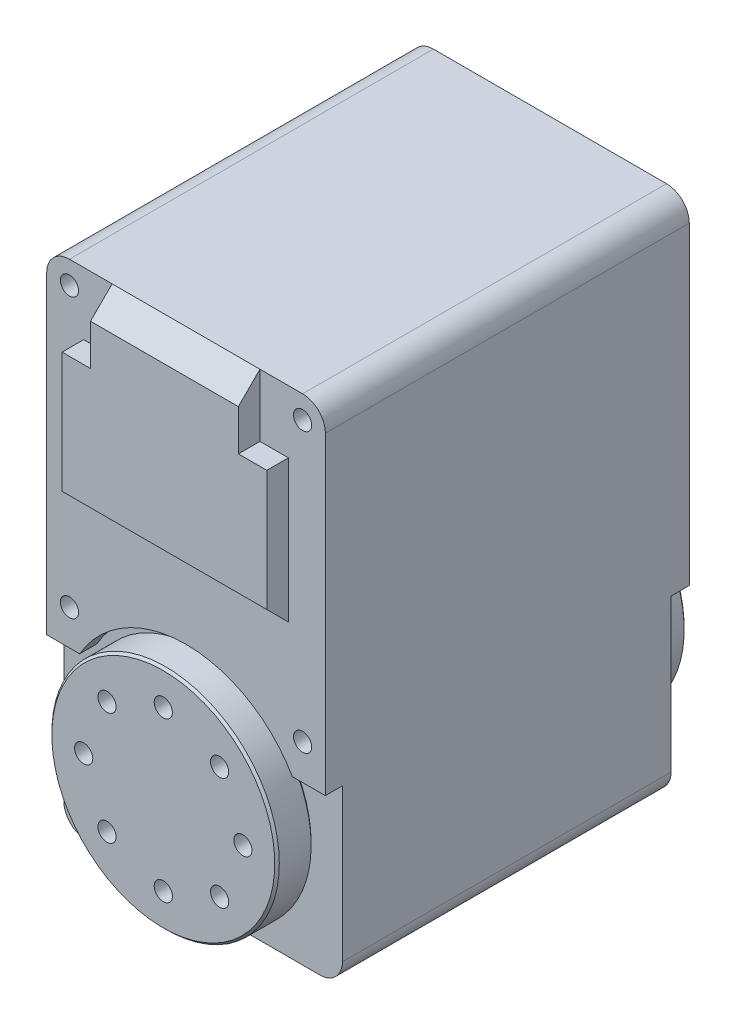
SolidWorks part; units mm, degrees
ref_plane "Front Plane" through (0, 0, 0) normal (0, 0, 1) x (1, 0, 0)
ref_plane "Top Plane" through (0, 0, 0) normal (0, 1, 0) x (1, 0, 0)
ref_plane "Right Plane" through (0, 0, 0) normal (1, 0, 0) x (0, 0, -1)
sketch "Sketch1" plane through (0, 0, 0) normal (0, 0, 1) x (1, 0, 0)
  line L1 (-10.25, 22.5) -> (10.25, 22.5)
  line L2 (-12.25, 20.5) -> (-12.25, -20.5)
  line L3 (-10.25, -22.5) -> (10.25, -22.5)
  line L4 (12.25, 20.5) -> (12.25, -20.5)
  line L5 (-12.25, 22.5) -> (12.25, -22.5) construction
  line L6 (-12.25, -22.5) -> (12.25, 22.5) construction
  arc A0 (10.25, -22.5) -> (12.25, -20.5) centre (10.25, -20.5) ccw
  arc A1 (-10.25, -22.5) -> (-12.25, -20.5) centre (-10.25, -20.5) cw
  arc A2 (12.25, 20.5) -> (10.25, 22.5) centre (10.25, 20.5) ccw
  arc A3 (-12.25, 20.5) -> (-10.25, 22.5) centre (-10.25, 20.5) cw
  point P0 (0, 0)
  dimension "D3" = 2
  dimension "D1" = 24.5
  dimension "D2" = 45
extrude "Boss-Extrude1" add sketch "Sketch1" along normal blind 32
sketch "Sketch2" plane through (0, 0, 32) normal (0, 0, 1) x (1, 0, 0)
  line L0 (-10.25, -22.5) -> (10.25, -22.5) construction
  line L1 (12.25, -20.5) -> (12.25, 20.5) construction
  line L2 (-12.25, 20.5) -> (-12.25, -20.5) construction
  line L3 (-12.25, -7.1) -> (12.25, -7.1)
  line L4 (-12.25, -7.1) -> (-12.25, -22.5)
  line L5 (-12.25, -22.5) -> (12.25, -22.5)
  line L6 (12.25, -7.1) -> (12.25, -22.5)
  circle A0 centre (0, -12.5) radius 10.8
  arc M5 (10.25, -22.5) -> (12.25, -20.5) centre (10.25, -20.5) ccw
  line M6 (12.25, -20.5) -> (12.25, 20.5)
  line M10 (-12.25, 20.5) -> (-12.25, -20.5)
  arc M11 (-12.25, -20.5) -> (-10.25, -22.5) centre (-10.25, -20.5) ccw
  line M12 (-10.25, -22.5) -> (10.25, -22.5)
  dimension "D1" = 21.6
  dimension "D2" = 10
  dimension "D3" = 12.25
  dimension "D4" = 0
  dimension "D5" = 0
  dimension "D6" = 15.4
extrude "Cut-Extrude1" cut sketch "Sketch2" against normal blind 1.5 contours L3 A0 | L3 A0 L5 | A0 L3 M12 M5 M6 | A0 L3 M10 M11 M12 region at (-10.3353, -16.6231, 32) region at (0, -4.8858, 32) region at (0, -14.2224, 32) region at (10.3353, -16.6231, 32)
sketch "Sketch3" plane through (0, 0, 0) normal (0, 0, -1) x (-1, 0, 0)
  line L0 (10.25, -22.5) -> (-10.25, -22.5) construction
  line L1 (12.25, 20.5) -> (12.25, -20.5) construction
  line L3 (-12.25, -7.1) -> (12.25, -7.1)
  line L4 (-12.25, -7.1) -> (-12.25, -22.5)
  line L5 (-12.25, -22.5) -> (12.25, -22.5)
  line L6 (12.25, -7.1) -> (12.25, -22.5)
  circle A0 centre (0, -12.5) radius 10.8
  dimension "D1" = 21.6
  dimension "D2" = 10
  dimension "D3" = 12.25
  dimension "D4" = 0
  dimension "D5" = 0
extrude "Cut-Extrude2" cut sketch "Sketch3" against normal blind 1.6 contours L3 A0 | L3 A0 L5 | L4 L5 L6 L3 region at (0, -4.8858, 0) region at (0, -14.2224, 0)
sketch "Sketch4" plane through (0, 0, 30.5) normal (0, 0, 1) x (1, 0, 0)
  circle A0 centre (0, -12.5) radius 3.2
  dimension "D1" = 6.4
extrude "Boss-Extrude2" add sketch "Sketch4" along normal blind 0.3 and the other way blind 29.3
sketch "Sketch5" plane through (0, 0, 30.8) normal (0, 0, 1) x (1, 0, 0)
  line L0 (12.25, -20.5) -> (12.25, -7.1) construction
  circle A0 centre (0, -12.5) radius 10
  circle A1 centre (0, -5.5) radius 0.8
  circle A2 centre (4.9497, -7.5503) radius 0.8
  circle A3 centre (7, -12.5) radius 0.8
  circle A4 centre (4.9497, -17.4497) radius 0.8
  circle A5 centre (0, -19.5) radius 0.8
  circle A6 centre (-4.9497, -17.4497) radius 0.8
  circle A7 centre (-7, -12.5) radius 0.8
  circle A8 centre (-4.9497, -7.5503) radius 0.8
  point P7 (6.5771, -10.1039)
  point P24 (0, -12.5)
  dimension "D1" = 20
  dimension "D2" = 1.6
  dimension "D3" = 7
  dimension "D6" = 7
  dimension "D7" = 7
  dimension "D4" = 12.25
  dimension "D5" = 8
extrude "Boss-Extrude3" add sketch "Sketch5" along normal blind 3.2
sketch "Sketch6" plane through (0, 0, 1.2) normal (0, 0, -1) x (-1, 0, 0)
  line L0 (12.25, 20.5) -> (12.25, -7.1) construction
  circle A0 centre (0, -12.5) radius 10
  circle A1 centre (0, -5.5) radius 0.8
  circle A2 centre (4.9497, -7.5503) radius 0.8
  circle A3 centre (7, -12.5) radius 0.8
  circle A4 centre (4.9497, -17.4497) radius 0.8
  circle A5 centre (0, -19.5) radius 0.8
  circle A6 centre (-4.9497, -17.4497) radius 0.8
  circle A7 centre (-7, -12.5) radius 0.8
  circle A8 centre (-4.9497, -7.5503) radius 0.8
  point P8 (0, 0)
  point P9 (0, -12.5)
  point P23 (0, -12.5)
  dimension "D1" = 20
  dimension "D2" = 1.6
  dimension "D3" = 7
  dimension "D4" = 12.25
  dimension "D5" = 8
extrude "Boss-Extrude5" add sketch "Sketch6" along normal blind 3.2
sketch "Sketch7" plane through (0, 0, 32) normal (0, 0, 1) x (1, 0, 0)
  line L0 (10.25, 22.5) -> (-10.25, 22.5) construction
  line L1 (-9, 22.5) -> (9, 22.5)
  line L2 (-9, 22.5) -> (-9, 4.5)
  line L3 (-9, 4.5) -> (9, 4.5)
  line L4 (9, 22.5) -> (9, 4.5)
  line L6 (-9, 22.5) -> (-6.5, 22.5)
  line L7 (-9, 22.5) -> (-9, 17)
  line L8 (-9, 17) -> (-6.5, 17)
  line L9 (-6.5, 22.5) -> (-6.5, 17)
  line L10 (9, 22.5) -> (6.5, 22.5)
  line L11 (9, 22.5) -> (9, 17)
  line L12 (9, 17) -> (6.5, 17)
  line L13 (6.5, 22.5) -> (6.5, 17)
  dimension "D1" = 18
  dimension "D2" = 9
  dimension "D3" = 18
  dimension "D4" = 5.5
  dimension "D5" = 5.5
  dimension "D6" = 2.5
  dimension "D7" = 2.5
extrude "Boss-Extrude6" add sketch "Sketch7" along normal blind 1.9 contours L13 L1 L9 L8 L2 L3 L4 L12 region at (0, 12.9203, 32)
chamfer "Chamfer1" distance 1.9 angle 45 2 edges at (0, 22.5, 33.9) (0, 4.5, 33.9)
sketch "Sketch8" plane through (0, 0, 0) normal (0, 0, -1) x (-1, 0, 0)
  line L0 (-10.25, 22.5) -> (10.25, 22.5) construction
  line L1 (-7, 22.5) -> (7, 22.5)
  line L2 (-7, 22.5) -> (-7, -7.5)
  line L3 (-7, -7.5) -> (7, -7.5)
  line L4 (7, 22.5) -> (7, -7.5)
  circle A0 centre (0, -12.5) radius 10.8
  arc M4 (-9.3531, -7.1) -> (9.3531, -7.1) centre (0, -12.5) cw
  line M8 (10.25, 22.5) -> (-10.25, 22.5)
  dimension "D4" = 21.6
  dimension "D1" = 14
  dimension "D2" = 7
  dimension "D3" = 30
extrude "Boss-Extrude7" add sketch "Sketch8" along normal blind 1.1 contours L4 L2 M8 M4 region at (0, 9.9823, 0)
chamfer "Chamfer2" distance 1.1 angle 45 1 edges at (0, 22.5, -1.1)
sketch "Sketch9" plane through (0, 0, 32) normal (0, 0, 1) x (1, 0, 0)
  line L0 (10.25, 22.5) -> (6.5, 22.5) construction
  line L1 (-6.5, 22.5) -> (-10.25, 22.5) construction
  line L2 (-12.25, 20.5) -> (-12.25, -7.1) construction
  line L3 (12.25, -7.1) -> (12.25, 20.5) construction
  circle A0 centre (-10.25, 20.5) radius 0.8
  circle A1 centre (10.25, 20.5) radius 0.8
  circle A2 centre (-10.25, -4) radius 0.8
  circle A3 centre (10.25, -4) radius 0.8
  dimension "D1" = 20.5
  dimension "D2" = 1.6
  dimension "D3" = 1.6
  dimension "D4" = 2
  dimension "D5" = 2
  dimension "D6" = 2
  dimension "D7" = 1.6
  dimension "D8" = 1.6
  dimension "D9" = 24.5
  dimension "D10" = 24.5
  dimension "D11" = 2
  dimension "D12" = 2
extrude "Cut-Extrude3" cut sketch "Sketch9" against normal offset from surface (3 mm away) 3 up to face at (0, 11.6143, 32)
sketch "Sketch10" plane through (0, 0, 0) normal (0, 0, -1) x (-1, 0, 0)
  line L0 (-12.25, -7.1) -> (-12.25, 20.5) construction
  line L1 (-10.25, 22.5) -> (-7, 22.5) construction
  line L2 (7, 22.5) -> (10.25, 22.5) construction
  line L3 (12.25, 20.5) -> (12.25, -7.1) construction
  circle A0 centre (-10.25, 20.5) radius 0.8
  circle A1 centre (10.25, 20.5) radius 0.8
  circle A2 centre (-10.25, -4) radius 0.8
  circle A3 centre (10.25, -4) radius 0.8
  dimension "D1" = 2
  dimension "D2" = 2
  dimension "D3" = 2
  dimension "D4" = 2
  dimension "D5" = 1.6
  dimension "D6" = 1.6
  dimension "D7" = 1.6
  dimension "D8" = 1.6
  dimension "D9" = 24.5
  dimension "D10" = 24.5
  dimension "D11" = 2
  dimension "D12" = 2
extrude "Cut-Extrude4" cut sketch "Sketch10" against normal blind 3
chamfer "Chamfer3" distance 0.2 angle 45 4 edges at (10, -12.5, 30.8) (-10, -12.5, 1.2) (-10, -12.5, -2) (10, -12.5, 34)
